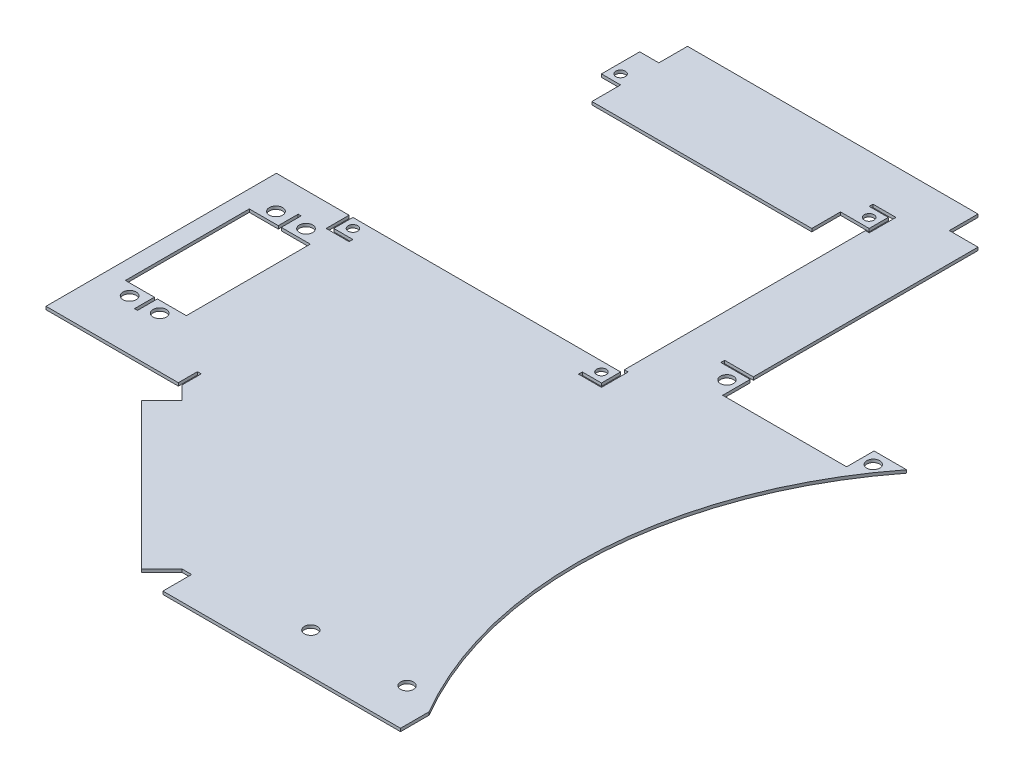
SolidWorks part; units mm, degrees
ref_plane "Front Plane" through (0, 0, 0) normal (0, 0, 1) x (1, 0, 0)
ref_plane "Top Plane" through (0, 0, 0) normal (0, 1, 0) x (1, 0, 0)
ref_plane "Right Plane" through (0, 0, 0) normal (1, 0, 0) x (0, 0, -1)
sketch "Sketch2" plane through (0, 0, 0) normal (0, 1, 0) x (1, 0, 0)
  line L1 (-127, -127) -> (127, -127)
  line L2 (-127, -127) -> (-127, 127)
  line L3 (-127, 127) -> (127, 127)
  line L4 (127, -127) -> (127, 127)
  line L5 (-127, -127) -> (127, 127) construction
  line L6 (-127, 127) -> (127, -127) construction
  point P0 (0, 0)
  dimension "D1" = 254
  dimension "D2" = 254
extrude "Boss-Extrude1" add sketch "Sketch2" along normal blind 1.0008 contours L3 L4 L1 L2
sketch "Sketch3" plane through (0, 1.0008, 0) normal (0, 1, 0) x (1, 0, 0)
  line L0 (63.5, 41.91) -> (63.5, 3.81) construction
  line L1 (127, 127) -> (60.96, 127)
  line L2 (127, 127) -> (127, 21.852)
  line L3 (127, 21.852) -> (60.96, 21.852)
  line L4 (60.96, 127) -> (60.96, 21.852)
  line L7 (64.096, 22.36) -> (70.7, 22.36) construction
  line L8 (64.096, 22.36) -> (70.7, 22.36) construction
  dimension "D1" = 2.54
  dimension "D2" = 0.508
extrude "Cut-Extrude1" cut sketch "Sketch3" against normal through all both and the other way through all
sketch "Sketch4" plane through (0, 1.0008, 0) normal (0, 1, 0) x (1, 0, 0)
  line L6 (127, -127) -> (127, 21.852)
  line L7 (127, 21.852) -> (60.96, 21.852)
  line L8 (60.96, 21.852) -> (60.96, 127)
  line L9 (60.96, 127) -> (-127, 127)
  line L10 (-127, 127) -> (-127, -127)
  line L11 (-127, -127) -> (127, -127)
  line L12 (127, -127) -> (127, 21.852)
  line L13 (127, 21.852) -> (122.64, 21.852)
  line L17 (112.9689, -127) -> (127, -127)
  arc A0 (127, 27.1603) -> (114.5024, -129.54) centre (227.33, -59.69) ccw construction
  arc A1 (122.64, 21.852) -> (112.9689, -127) centre (227.33, -59.69) ccw
  dimension "D1" = 0
extrude "Cut-Extrude2" cut sketch "Sketch4" against normal through all both
sketch "Sketch5" plane through (0, 1.0008, 0) normal (0, 1, 0) x (1, 0, 0)
  line L0 (63.5, -129.54) -> (63.5, -61.2891) construction
  circle A0 centre (115.577, 17.86) radius 2.1 construction
  circle A1 centre (66.977, 17.86) radius 2.1 construction
  circle A2 centre (115.577, 17.86) radius 2.1 construction
  circle A3 centre (66.977, 17.86) radius 2.1 construction
  circle A4 centre (69.85, -123.19) radius 2.15
  circle A5 centre (101.8024, -123.19) radius 2.15
  circle A6 centre (66.977, 17.86) radius 2.15
  circle A7 centre (115.577, 17.86) radius 2.15
  dimension "D5" = 4.3
  dimension "D1" = 6.35
  dimension "D2" = 12.7
  dimension "D3" = 6.35
  dimension "D4" = 6.35
extrude "Cut-Extrude3" cut sketch "Sketch5" against normal through all both
sketch "Sketch6" plane through (0, 1.0008, 0) normal (0, 1, 0) x (1, 0, 0)
  line L12 (70.7, 22.36) -> (70.7, 12.733)
  line L13 (70.7, 12.733) -> (111.854, 12.733)
  line L14 (111.854, 12.733) -> (111.854, 22.36)
  line L15 (111.854, 22.36) -> (118.458, 22.36)
  line L16 (118.458, 22.36) -> (118.458, 23.36)
  line L17 (118.458, 23.36) -> (111.854, 23.36)
  line L18 (111.854, 23.36) -> (111.854, 32.987)
  line L19 (111.854, 32.987) -> (70.7, 32.987)
  line L20 (70.7, 32.987) -> (70.7, 23.36)
  line L21 (70.7, 23.36) -> (64.096, 23.36)
  line L22 (64.096, 23.36) -> (64.096, 22.36)
  line L23 (64.096, 22.36) -> (70.7, 22.36)
  line L24 (70.7, 22.36) -> (70.7, 12.733)
  line L25 (70.7, 12.733) -> (111.854, 12.733)
  line L26 (111.854, 12.733) -> (111.854, 22.36)
  line L27 (111.854, 22.36) -> (118.458, 22.36)
  line L28 (118.458, 22.36) -> (118.458, 23.36)
  line L29 (118.458, 23.36) -> (111.854, 23.36)
  line L30 (111.854, 23.36) -> (111.854, 32.987)
  line L31 (111.854, 32.987) -> (70.7, 32.987)
  line L32 (70.7, 32.987) -> (70.7, 23.36)
  line L33 (70.7, 23.36) -> (64.096, 23.36)
  line L34 (64.096, 23.36) -> (64.096, 22.36)
  line L35 (64.096, 22.36) -> (70.7, 22.36)
  circle A1 centre (66.977, 27.86) radius 2.1
  circle A2 centre (66.977, 27.86) radius 2.1
  circle A3 centre (66.977, 17.86) radius 2.1
  circle A4 centre (66.977, 17.86) radius 2.1
  circle A5 centre (115.577, 27.86) radius 2.1
  circle A6 centre (115.577, 27.86) radius 2.1
  circle A7 centre (115.577, 17.86) radius 2.1
  circle A8 centre (115.577, 17.86) radius 2.1
  dimension "D1" = 0
  dimension "D2" = 0
  dimension "D3" = 0
  dimension "D4" = 0
  dimension "D5" = 0
extrude "Cut-Extrude4" cut sketch "Sketch6" against normal through all both
sketch "Sketch7" plane through (0, 1.0008, 0) normal (0, 1, 0) x (1, 0, 0)
  line L1 (-35.5092, 2.4892) -> (47.0408, 2.4892)
  line L2 (-35.5092, 2.4892) -> (-35.5092, 85.0392)
  line L3 (-35.5092, 85.0392) -> (47.0408, 85.0392)
  line L4 (47.0408, 2.4892) -> (47.0408, 85.0392)
  line L5 (-35.5092, 2.4892) -> (47.0408, 85.0392) construction
  line L6 (-35.5092, 85.0392) -> (47.0408, 2.4892) construction
  circle A2 centre (101.6, 22.86) radius 4.7625 construction
  circle A3 centre (101.6, 22.86) radius 4.699 construction
  point P0 (5.7658, 43.7642)
  dimension "D1" = 82.55
  dimension "D3" = 20.3708
  dimension "D2" = 137.1092
extrude "Cut-Extrude5" cut sketch "Sketch7" against normal through all both
sketch "Sketch8" plane through (0, 1.0008, 0) normal (0, 1, 0) x (1, 0, 0)
  line L0 (60.96, 97.7392) -> (60.96, 127)
  line L1 (60.96, 21.852) -> (60.96, 127) construction
  line L2 (60.96, 127) -> (-127, 127)
  line L3 (-127, 127) -> (-127, -127)
  line L4 (-127, -127) -> (-35.5092, -127)
  line L5 (-127, -127) -> (112.9689, -127) construction
  line L6 (-35.5092, -127) -> (-35.5092, 97.7392)
  line L7 (-35.5092, 97.7392) -> (60.96, 97.7392)
  line L8 (47.0408, 85.0392) -> (-35.5092, 85.0392) construction
  line L9 (-35.5092, 85.0392) -> (-35.5092, 2.4892) construction
  dimension "D1" = 12.7
extrude "Cut-Extrude6" cut sketch "Sketch8" against normal through all both
sketch "Sketch9" plane through (0, 1.0008, 0) normal (0, 1, 0) x (1, 0, 0)
  line L0 (-35.5092, -60.5651) -> (30.9257, -127)
  line L1 (-35.5092, -127) -> (-35.5092, 2.4892) construction
  line L2 (-35.5092, -127) -> (112.9689, -127) construction
  line L3 (-35.5092, -127) -> (30.9257, -127)
  line L4 (-35.5092, -127) -> (-35.5092, -60.5651)
  circle A0 centre (101.727, 22.86) radius 149.6811 construction
  circle A1 centre (101.727, 22.86) radius 156.0311 construction
  dimension "D1" = 6.35
  dimension "D2" = 45
extrude "Cut-Extrude7" cut sketch "Sketch9" against normal through all both
sketch "Sketch10" plane through (0, 1.0008, 0) normal (0, 1, 0) x (1, 0, 0)
  line L0 (-17.5487, -78.5256) -> (30.8851, -126.9594)
  line L1 (30.8851, -126.9594) -> (24.1499, -133.6946)
  line L2 (24.1499, -133.6946) -> (-24.2839, -85.2608)
  line L3 (-24.2839, -85.2608) -> (-17.5487, -78.5256)
  line L4 (-35.5092, 2.4892) -> (-41.8592, 2.4892)
  line L5 (-41.8592, 2.4892) -> (-41.8592, -3.8608)
  line L6 (-41.8592, -3.8608) -> (-35.5092, -3.8608)
  line L7 (-35.5092, -60.5651) -> (-35.5092, 2.4892) construction
  line L8 (-35.5092, -3.8608) -> (-35.5092, 2.4892)
  line L9 (70.7, 21.852) -> (60.96, 21.852) construction
  line L10 (60.96, 97.7392) -> (70.485, 97.7392)
  line L11 (60.96, 97.7392) -> (60.96, 23.122)
  line L12 (60.96, 23.122) -> (70.485, 23.122)
  line L13 (70.485, 97.7392) -> (70.485, 23.122)
  line L14 (47.0408, 2.4892) -> (47.0408, 85.0392) construction
  line L15 (-35.5092, 97.7392) -> (60.96, 97.7392)
  line L16 (-35.5092, 97.7392) -> (-35.5092, 107.2642)
  line L17 (-35.5092, 107.2642) -> (60.96, 107.2642)
  line L18 (60.96, 97.7392) -> (60.96, 107.2642)
  line L19 (-35.5092, 85.0392) -> (-41.8592, 85.0392)
  line L20 (-35.5092, 85.0392) -> (-35.5092, 97.7392)
  line L21 (-35.5092, 97.7392) -> (-41.8592, 97.7392)
  line L22 (-41.8592, 85.0392) -> (-41.8592, 97.7392)
  line L27 (-35.5092, 85.0392) -> (37.5158, 85.0392)
  line L28 (-35.5092, 85.0392) -> (-35.5092, 75.5142)
  line L29 (-35.5092, 75.5142) -> (37.5158, 75.5142)
  line L30 (37.5158, 85.0392) -> (37.5158, 75.5142)
  line L31 (30.9257, -127) -> (-35.5092, -60.5651) construction
  line L33 (112.9689, -127) -> (34.0601, -127)
  line L34 (112.9689, -127) -> (112.9689, -136.525)
  line L35 (112.9689, -136.525) -> (34.0601, -136.525)
  line L36 (34.0601, -127) -> (34.0601, -136.525)
  line M23 (-35.5092, -60.5651) -> (30.9257, -127)
  line M24 (30.9257, -127) -> (112.9689, -127)
  line M31 (60.96, 21.852) -> (60.96, 97.7392)
  line M32 (60.96, 97.7392) -> (-35.5092, 97.7392)
  line M33 (-35.5092, 97.7392) -> (-35.5092, 85.0392)
  dimension "D1" = 9.525
  dimension "D2" = 6.35
  dimension "D3" = 6.35
  dimension "D4" = 6.35
  dimension "D5" = 1.27
  dimension "D6" = 9.525
  dimension "D7" = 25.4
  dimension "D8" = 3.175
extrude "Boss-Extrude2" add sketch "Sketch10" against normal up to surface (1.0008 mm away) contours L3 L2 L1 M23 | L35 L34 M24 | L13 L10 L12 M31 | L18 L17 L16 M32 | L22 L19 L21 M33 | L6 L8 L4 L5 | L28 L27 L30 L29 region at (73.5145, 1.0008, 131.7625) region at (3.3006, 1.0008, 106.1101) region at (65.7225, 1.0008, -60.4306) region at (-38.6842, 1.0008, -91.3892) region at (12.7254, 1.0008, -102.5017) up to face at (45.5142, 0, -11.3554)
sketch "Sketch11" plane through (0, 1.0008, 0) normal (0, 1, 0) x (1, 0, 0)
  line L0 (47.0408, 91.3892) -> (47.0408, 85.0392)
  line L2 (40.6908, 91.3892) -> (47.0408, 91.3892)
  line L3 (47.0408, 43.7642) -> (-71.8083, 43.7642) construction
  line L5 (47.0408, 85.0392) -> (37.5158, 85.0392) construction
  line L6 (40.6908, 92.6592) -> (48.3108, 92.6592)
  line L7 (47.0408, 2.4892) -> (47.0408, 85.0392) construction
  line L8 (48.3108, 92.6592) -> (48.3108, 85.0392)
  line L9 (40.6908, 92.6592) -> (40.6908, 91.3892)
  line L10 (48.3108, 85.0392) -> (48.3108, 83.7692)
  line L11 (48.3108, 83.7692) -> (47.0408, 83.7692)
  line L12 (47.0408, 83.7692) -> (47.0408, 85.0392)
  dimension "D1" = 6.35
  dimension "D2" = 6.35
  dimension "D4" = 1.27
  dimension "D3" = 1.27
sketch "Sketch12" plane through (0, 1.0008, 0) normal (0, 1, 0) x (1, 0, 0)
  line L8 (-41.8592, 85.0392) -> (-41.8592, 97.7392) construction
  line L9 (-35.5092, 85.0392) -> (-41.8592, 85.0392) construction
  line L10 (47.0408, 2.4892) -> (47.0408, 85.0392) construction
  circle A2 centre (43.8658, 88.2142) radius 1.5875
  circle A3 centre (-38.6842, 88.2142) radius 1.5875
  point P4 (0, 0)
  dimension "D1" = 3.175
  dimension "D2" = 3.175
  dimension "D3" = 3.175
  dimension "D4" = 3.175
extrude "Cut-Extrude8" cut sketch "Sketch12" against normal through all both
extrude "Cut-Extrude9" cut sketch "Sketch11" against normal through all both
sketch "Sketch13" plane through (0, 1.0008, 0) normal (0, 1, 0) x (1, 0, 0)
  line L0 (47.0408, 43.7642) -> (-64.9581, 43.7642) construction
  line L3 (-41.8592, 85.0392) -> (-41.8592, 43.7642) construction
  line L4 (-41.8592, 43.7642) -> (-41.8592, 2.4892) construction
ref_plane "Plane1" through (0, 0, -43.7642) normal (0, 0, 1) x (1, 0, 0)
mirror "Mirror1" about plane through (0, 0, -43.7642) normal (0, 0, 1) of "Cut-Extrude9", "Cut-Extrude8"
sketch "Sketch14" plane through (0, 1.0008, 0) normal (0, 1, 0) x (1, 0, 0)
  line L0 (-61.5112, -12.271) -> (-41.2572, -53.425) construction
  line L5 (-61.5112, -12.271) -> (-51.8842, -12.271)
  line L6 (-61.5112, -12.271) -> (-61.5112, -53.425)
  line L7 (-61.5112, -53.425) -> (-51.8842, -53.425)
  line L12 (-41.2572, -12.271) -> (-41.2572, -53.425)
  line L17 (-35.5092, -5.1308) -> (-67.2592, -5.1308)
  line L22 (-35.5092, -60.5651) -> (-35.5092, -3.8608) construction
  line L23 (-67.2592, -5.1308) -> (-67.2592, -60.5651)
  line L24 (-67.2592, -60.5651) -> (-35.5092, -60.5651)
  line L25 (-35.5092, -60.5651) -> (-35.5092, -5.1308)
  line L34 (-41.2572, -12.271) -> (-61.5112, -53.425) construction
  line L35 (-56.3842, -8.548) -> (-46.3842, -57.148) construction
  line L36 (-56.3842, -57.148) -> (-46.3842, -8.548) construction
  line L37 (-50.8842, -53.425) -> (-41.2572, -53.425)
  line L38 (-51.8842, -53.425) -> (-51.8842, -60.029)
  line L39 (-51.8842, -60.029) -> (-50.8842, -60.029)
  line L40 (-50.8842, -53.425) -> (-50.8842, -60.029)
  line L41 (-51.3842, -32.848) -> (-15.6253, -32.848) construction
  line L42 (-51.8842, -5.667) -> (-50.8842, -5.667)
  line L43 (-51.8842, -12.271) -> (-51.8842, -5.667)
  line L44 (-50.8842, -12.271) -> (-50.8842, -5.667)
  line L45 (-50.8842, -12.271) -> (-41.2572, -12.271)
  line L46 (-41.8592, -3.8608) -> (-35.5092, -3.8608) construction
  line L47 (-67.2592, -5.1308) -> (-67.2592, 2.4892)
  line L48 (-67.2592, 2.4892) -> (-43.1292, 2.4892)
  line L49 (-43.1292, 2.4892) -> (-43.1292, -5.1308)
  line L50 (-41.8592, 2.4892) -> (47.0408, 2.4892) construction
  line L51 (-41.8592, 2.4892) -> (-41.8592, -3.8608) construction
  line L52 (-67.2592, -60.5651) -> (-67.2592, -74.0355)
  line L53 (-67.2592, -74.0355) -> (-22.0388, -74.0355)
  line L54 (-17.5487, -78.5256) -> (-35.5092, -60.5651) construction
  line L57 (-22.0388, -74.0355) -> (-35.5092, -60.5651)
  circle A8 centre (-56.3842, -57.148) radius 2.2
  circle A9 centre (-46.3842, -57.148) radius 2.2
  circle A10 centre (-56.3842, -8.548) radius 2.2
  circle A11 centre (-46.3842, -8.548) radius 2.2
  point P9 (-51.3842, -60.029)
  point P19 (-51.3842, -32.848)
  point P20 (-51.3842, -32.848)
  point P37 (-67.2592, -32.848)
  point P39 (-51.3842, -60.5651)
  dimension "D3" = 48.6
  dimension "D4" = 4.4
  dimension "D1" = 1.27
  dimension "D2" = 10
  dimension "D5" = 41.154
  dimension "D6" = 20.254
  dimension "D7" = 1
  dimension "D8" = 6.604
  dimension "D9" = 31.75
  dimension "D10" = 1.27
  dimension "D11" = 6.35
extrude "Boss-Extrude3" add sketch "Sketch14" against normal up to surface (1.0008 mm away) contours L49 L48 L47 L17 | L24 L25 L17 L23 A11 A10 A9 A8 L44 L45 L12 L37 L40 L39 L38 L7 L6 L5 L43 L42 | L24 region at (-36.148, 1.0008, 32.848) region at (-55.1942, 1.0008, 1.3208) region at (-47.8202, 1.0008, 67.6932) up to face at (43.8658, 0, -0.9017)
sketch "Sketch15" plane through (0, 1.0008, 0) normal (0, 1, 0) x (1, 0, 0)
  line L0 (-22.0388, -74.0355) -> (-22.0388, -67.6855)
  dimension "D1" = 6.35
extrude "Cut-Extrude-Thin3" cut sketch "Sketch15" against normal through all both and the other way through all thin thin type one direction reverse wall 1.27
equation "\"looseTol\" = 0.02in"
equation "\"tightTol\" = 0.005in"
equation "\"normTol\" = 0.01in"
equation "\"D2@Sketch3\"=\"looseTol\""
equation "\"D5@Sketch5\"=4.3mm"
